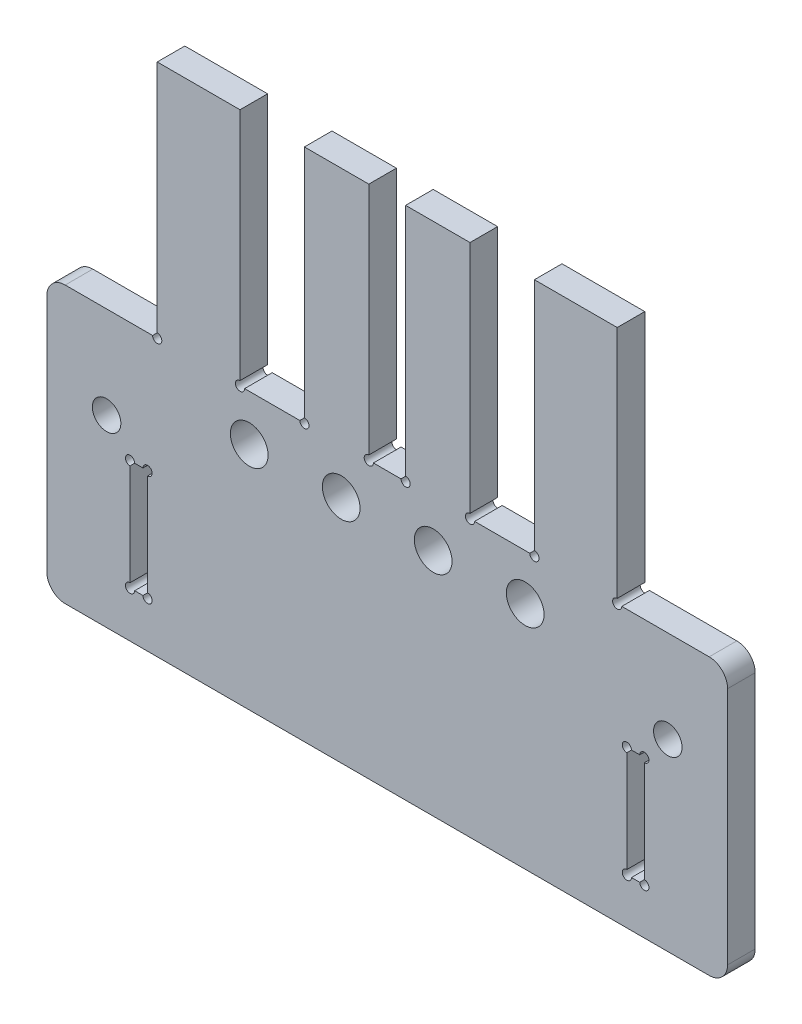
SolidWorks part; units mm, degrees
material "Thornel Mat VMA"
ref_plane "前视基准面" through (0, 0, 0) normal (0, 0, 1) x (1, 0, 0)
ref_plane "上视基准面" through (0, 0, 0) normal (0, 1, 0) x (1, 0, 0)
ref_plane "右视基准面" through (0, 0, 0) normal (1, 0, 0) x (0, 0, -1)
sketch "草图1" plane through (0, 0, 0) normal (0, 0, 1) x (1, 0, 0)
  line L1 (-37, -26.75) -> (37, -26.75)
  line L2 (-37, -26.75) -> (-37, 26.75)
  line L3 (-37, 26.75) -> (37, 26.75)
  line L4 (37, -26.75) -> (37, 26.75)
  line L5 (-37, -26.75) -> (37, 26.75) construction
  line L6 (-37, 26.75) -> (37, -26.75) construction
  point P0 (0, 0)
  dimension "D1" = 53.5
  dimension "D2" = 74
extrude "凸台-拉伸1" add sketch "草图1" along normal blind 3
sketch "草图2" plane through (0, 0, 0) normal (0, 0, -1) x (-1, 0, 0)
  line L0 (-37, -26.75) -> (-37, 26.75) construction
  line L1 (26, -24.25) -> (28, -24.25)
  line L2 (26, -24.25) -> (26, -12.25)
  line L3 (26, -12.25) -> (28, -12.25)
  line L4 (28, -24.25) -> (28, -12.25)
  line L5 (-28, -24.25) -> (-26, -24.25)
  line L6 (-28, -24.25) -> (-28, -12.25)
  line L7 (-28, -12.25) -> (-26, -12.25)
  line L8 (-26, -24.25) -> (-26, -12.25)
  line L9 (37, 26.75) -> (37, -26.75) construction
  line L10 (37, -26.75) -> (-37, -26.75) construction
  circle A0 centre (30.5, -9.25) radius 1.55
  circle A1 centre (-30.5, -9.25) radius 1.55
  dimension "D13" = 3.1
  dimension "D14" = 3.1
  dimension "D1" = 9
  dimension "D2" = 9
  dimension "D3" = 2.5
  dimension "D4" = 2.5
  dimension "D5" = 12
  dimension "D6" = 12
  dimension "D7" = 2
  dimension "D8" = 2
  dimension "D9" = 6.5
  dimension "D10" = 17.5
  dimension "D11" = 6.5
  dimension "D12" = 17.5
extrude "切除-拉伸1" cut sketch "草图2" against normal blind 5
sketch "草图3" plane through (0, 0, 0) normal (0, 0, -1) x (-1, 0, 0)
  line L0 (37, 26.75) -> (37, -26.75) construction
  line L1 (37, 0.75) -> (25, 0.75)
  line L2 (37, 0.75) -> (37, 26.75)
  line L3 (37, 26.75) -> (25, 26.75)
  line L4 (25, 0.75) -> (25, 26.75)
  line L5 (-37, 26.75) -> (37, 26.75) construction
  line L6 (37, -26.75) -> (-37, -26.75) construction
  line L7 (-37, -26.75) -> (-37, 26.75) construction
  line L8 (-37, 0.75) -> (-25, 0.75)
  line L9 (-37, 0.75) -> (-37, 26.75)
  line L10 (-37, 26.75) -> (-25, 26.75)
  line L11 (-25, 0.75) -> (-25, 26.75)
  line L13 (-16, 0.75) -> (-9, 0.75)
  line L14 (-16, 0.75) -> (-16, 26.75)
  line L15 (-16, 26.75) -> (-9, 26.75)
  line L16 (-9, 0.75) -> (-9, 26.75)
  line L17 (-2, 0.75) -> (2, 0.75)
  line L18 (-2, 0.75) -> (-2, 26.75)
  line L19 (-2, 26.75) -> (2, 26.75)
  line L20 (2, 0.75) -> (2, 26.75)
  line L21 (9, 0.75) -> (16, 0.75)
  line L22 (9, 0.75) -> (9, 26.75)
  line L23 (9, 26.75) -> (16, 26.75)
  line L24 (16, 0.75) -> (16, 26.75)
  dimension "D1" = 27.5
  dimension "D2" = 12
  dimension "D3" = 12
  dimension "D4" = 27.5
  dimension "D5" = 7
  dimension "D6" = 4
  dimension "D7" = 7
  dimension "D8" = 9
  dimension "D9" = 9
  dimension "D10" = 7
extrude "切除-拉伸2" cut sketch "草图3" against normal through all
sketch "草图4" plane through (0, 0, 0) normal (0, 0, -1) x (-1, 0, 0)
  line L0 (-2, 0.75) -> (2, 0.75) construction
  circle A0 centre (0, -14.25) radius 2.5
  dimension "D1" = 5
  dimension "D2" = 15
extrude "切除-拉伸3" [suppressed] cut sketch "草图4" against normal through all
sketch "草图5" plane through (0, 0, 0) normal (0, 0, -1) x (-1, 0, 0)
  line L0 (26, -12.25) -> (26, -24.25) construction
  line L1 (9, 0.75) -> (16, 0.75) construction
  line L2 (-16, 0.75) -> (-9, 0.75) construction
  line L3 (-26, -24.25) -> (-26, -12.25) construction
  circle A0 centre (18, -14.25) radius 2.5
  circle A1 centre (-18, -14.25) radius 2.5
  dimension "D1" = 5
  dimension "D4" = 5
  dimension "D2" = 8
  dimension "D3" = 15
  dimension "D5" = 15
  dimension "D6" = 8
extrude "切除-拉伸4" [suppressed] cut sketch "草图5" against normal blind 10
sketch "草图6" plane through (0, 0, 0) normal (0, 0, -1) x (-1, 0, 0)
  line L0 (0, 7.589) -> (0, -30.5527) construction
  line L1 (-16, 0.75) -> (-9, 0.75) construction
  circle A0 centre (-15, -9.25) radius 2.5
  circle A1 centre (15, -9.25) radius 2.5
  dimension "D1" = 5
  dimension "D2" = 5
  dimension "D3" = 15
  dimension "D4" = 15
  dimension "D5" = 10
sketch "草图7" plane through (0, 0, 0) normal (0, 0, -1) x (-1, 0, 0)
  circle A0 centre (-25, 0.75) radius 0.5
  circle A1 centre (-16, 0.75) radius 0.5
  circle A2 centre (-9, 0.75) radius 0.5
  circle A3 centre (-2, 0.75) radius 0.5
  circle A4 centre (2, 0.75) radius 0.5
  circle A5 centre (9, 0.75) radius 0.5
  circle A6 centre (16, 0.75) radius 0.5
  circle A7 centre (25, 0.75) radius 0.5
  dimension "D1" = 1
sketch "草图8" plane through (0, 0, 0) normal (0, 0, -1) x (-1, 0, 0)
  line L0 (37, -26.75) -> (37, -29.25)
  line L1 (37, -26.75) -> (-37, -26.75) construction
  line L2 (37, -29.25) -> (-37, -29.25)
  line L3 (-37, -29.25) -> (-37, -26.75)
  line L4 (-37, -26.75) -> (37, -26.75)
  line L5 (-37, -26.75) -> (-37, 0.75) construction
  line L6 (37, 0.75) -> (37, -26.75) construction
  dimension "D1" = 2.5
extrude "凸台-拉伸2" add sketch "草图8" against normal blind 3
fillet "圆角1" radius 2 4 edges at (-37, 0.75, 1.5) (37, 0.75, 1.5) (37, -29.25, 1.5) (-37, -29.25, 1.5)
extrude "切除-拉伸6" cut sketch "草图7" against normal blind 10
sketch "草图10" plane through (0, 0, 0) normal (0, 0, -1) x (-1, 0, 0)
  line L0 (28, -12.25) -> (26, -12.25) construction
  line L1 (28, -24.25) -> (27.95, -24.25)
  line L2 (28, -24.25) -> (28, -12.25)
  line L3 (28, -12.25) -> (27.95, -12.25)
  line L4 (27.95, -24.25) -> (27.95, -12.25)
  line L5 (26, -24.25) -> (28, -24.25) construction
  line L6 (26, -24.25) -> (26.05, -24.25)
  line L7 (26, -24.25) -> (26, -12.25)
  line L8 (26, -12.25) -> (26.05, -12.25)
  line L9 (26.05, -24.25) -> (26.05, -12.25)
  line L10 (26, -12.25) -> (26, -24.25) construction
  line L11 (-26, -12.25) -> (-28, -12.25) construction
  line L12 (-26, -24.25) -> (-26.05, -24.25)
  line L13 (-26, -24.25) -> (-26, -12.25)
  line L14 (-26, -12.25) -> (-26.05, -12.25)
  line L15 (-26.05, -24.25) -> (-26.05, -12.25)
  line L17 (-28, -24.25) -> (-27.95, -24.25)
  line L18 (-28, -24.25) -> (-28, -12.25)
  line L19 (-28, -12.25) -> (-27.95, -12.25)
  line L20 (-27.95, -24.25) -> (-27.95, -12.25)
  dimension "D1" = 0.05
  dimension "D2" = 0.05
  dimension "D3" = 0.05
  dimension "D4" = 0.05
extrude "凸台-拉伸3" add sketch "草图10" against normal up to surface (3 mm away) up to face at (0, 3.4741, 3)
sketch "草图11" plane through (0, 0, 0) normal (0, 0, -1) x (-1, 0, 0)
  circle A0 centre (27.95, -24.25) radius 0.5
  circle A1 centre (26.05, -24.25) radius 0.5
  circle A2 centre (27.95, -12.25) radius 0.5
  circle A3 centre (26.05, -12.25) radius 0.5
  circle A4 centre (-26.05, -24.25) radius 0.5
  circle A5 centre (-27.95, -24.25) radius 0.5
  circle A6 centre (-27.95, -12.25) radius 0.5
  circle A7 centre (-26.05, -12.25) radius 0.5
  dimension "D1" = 1
extrude "切除-拉伸7" cut sketch "草图11" against normal blind 10
sketch "草图12" plane through (0, 0, 0) normal (0, 0, -1) x (-1, 0, 0)
  line L0 (0, 0) -> (0, -29.25) construction
  line L1 (0, 7.589) -> (0, -30.5527) construction
  line L2 (-35, -29.25) -> (35, -29.25) construction
  line L3 (-40.9315, -4.25) -> (41.2715, -4.25) construction
  line L4 (-35, 0.75) -> (-25.5, 0.75) construction
  line L5 (-37, -27.25) -> (-37, -1.25) construction
  circle A0 centre (-15, -4.25) radius 2.05
  circle A2 centre (-5, -4.25) radius 2.05
  circle A3 centre (5, -4.25) radius 2.05
  circle A4 centre (15, -4.25) radius 2.05
  dimension "D2" = 4.1
  dimension "D4" = 2
  dimension "D1" = 5
  dimension "D3" = 22
  dimension "D5" = 10
extrude "切除-拉伸8" cut sketch "草图12" against normal blind 10
